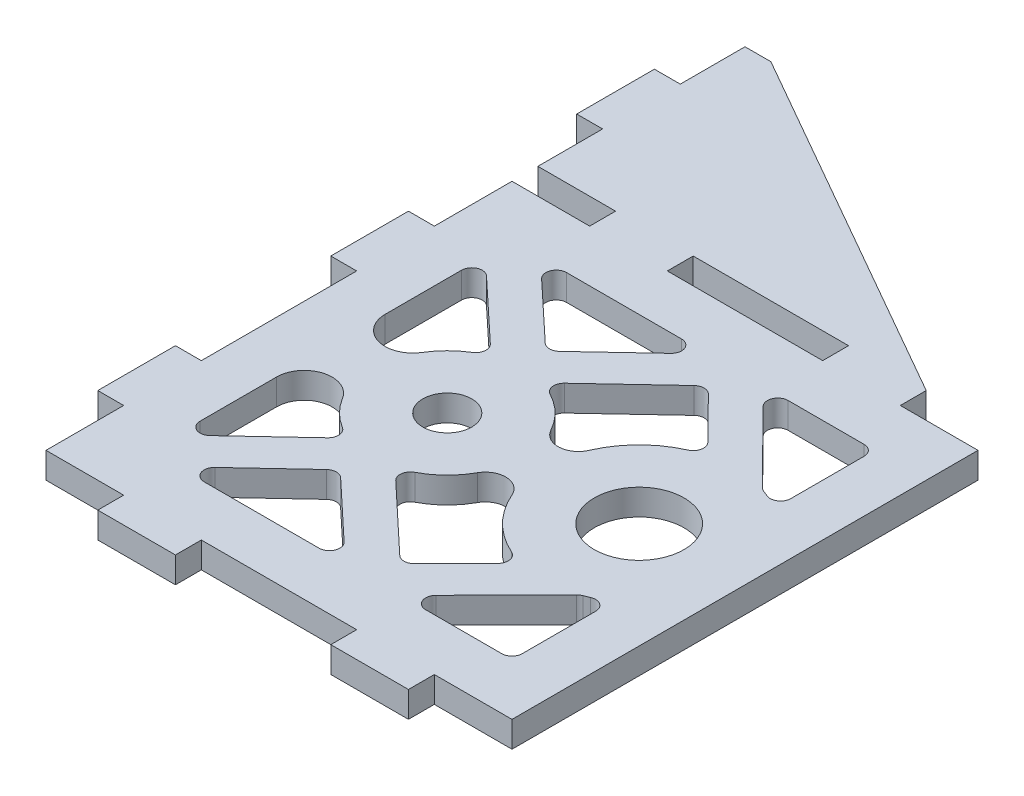
SolidWorks part; units mm, degrees
ref_plane "Front Plane" through (0, 0, 0) normal (0, 0, 1) x (1, 0, 0)
ref_plane "Top Plane" through (0, 0, 0) normal (0, 1, 0) x (1, 0, 0)
ref_plane "Right Plane" through (0, 0, 0) normal (1, 0, 0) x (0, 0, -1)
sketch "Sketch1" plane through (0, 0, 0) normal (0, 1, 0) x (1, 0, 0)
  line L0 (0, 57.15) -> (184.6638, 57.15) construction
  line L1 (0, 0) -> (19.05, 0)
  line L2 (0, 0) -> (0, 19.05)
  line L3 (0, 114.3) -> (19.05, 114.3)
  line L4 (114.3, 0) -> (114.3, 114.3)
  line L5 (38.1, 0) -> (76.2, 0)
  line L7 (95.25, 0) -> (95.25, -6.35)
  line L8 (95.25, -6.35) -> (76.2, -6.35)
  line L9 (76.2, 0) -> (76.2, -6.35)
  line L11 (19.05, 0) -> (19.05, -6.35)
  line L12 (19.05, -6.35) -> (38.1, -6.35)
  line L13 (38.1, 0) -> (38.1, -6.35)
  line L14 (95.25, 0) -> (114.3, 0)
  line L15 (38.1, 114.3) -> (38.1, 120.65)
  line L16 (19.05, 120.65) -> (38.1, 120.65)
  line L17 (19.05, 114.3) -> (19.05, 120.65)
  line L18 (76.2, 114.3) -> (76.2, 120.65)
  line L19 (95.25, 120.65) -> (76.2, 120.65)
  line L20 (95.25, 114.3) -> (95.25, 120.65)
  line L21 (38.1, 114.3) -> (76.2, 114.3)
  line L23 (95.25, 114.3) -> (114.3, 114.3)
  line L24 (-6.35, 19.05) -> (-6.35, 38.1)
  line L25 (0, 95.25) -> (-6.35, 95.25)
  line L27 (0, 76.2) -> (-6.35, 76.2)
  line L28 (-6.35, 95.25) -> (-6.35, 76.2)
  line L29 (0, 38.1) -> (-6.35, 38.1)
  line L31 (0, 19.05) -> (-6.35, 19.05)
  line L32 (0, 95.25) -> (0, 114.3)
  line L33 (0, 38.1) -> (0, 76.2)
  dimension "D1" = 114.3
  dimension "D2" = 114.3
  dimension "D3" = 19.05
  dimension "D4" = 19.05
  dimension "D5" = 19.05
  dimension "D6" = 19.05
  dimension "D7" = 6.35
  dimension "D8" = 6.35
  dimension "D9" = 19.05
  dimension "D10" = 19.05
extrude "Boss-Extrude1" add sketch "Sketch1" against normal blind 6.35
sketch "Sketch5" plane through (0, 0, 0) normal (0, 1, 0) x (1, 0, 0)
  line L0 (114.3, 57.15) -> (5.9998, 57.15) construction
  line L1 (114.3, 0) -> (114.3, 114.3) construction
  line L2 (3.175, 78.7113) -> (3.175, 29.9896) construction
  line L3 (0, 76.2) -> (0, 38.1) construction
  circle A0 centre (88.3412, 57.15) radius 10.16 construction
  circle A1 centre (41.275, 57.15) radius 38.1 construction
  dimension "D1" = 20.32
  dimension "D2" = 76.2
  dimension "D4" = 3.175
  dimension "D3" = 47.0662
sketch "Sketch2" plane through (0, 0, 0) normal (0, 1, 0) x (1, 0, 0)
  circle A2 centre (88.3412, 57.15) radius 11
  circle A3 centre (88.3412, 57.15) radius 10.16 construction
  circle A4 centre (88.3412, 57.15) radius 10.16 construction
  circle A5 centre (41.275, 57.15) radius 38.1 construction
  circle A6 centre (41.275, 57.15) radius 38.1 construction
  circle A7 centre (41.275, 57.15) radius 6
  dimension "D1" = 12
  dimension "D2" = 22
extrude "Cut-Extrude1" cut sketch "Sketch2" against normal through all
sketch "Sketch6" plane through (0, 0, 0) normal (0, 1, 0) x (1, 0, 0)
  line L28 (12.7, 101.6) -> (40.2169, 75.82) construction
  line L29 (15.9561, 105.0755) -> (43.4731, 79.2955)
  line L30 (9.4439, 98.1245) -> (36.9608, 72.3445)
  line L31 (40.2169, 75.82) -> (67.6542, 101.6) construction
  line L32 (36.9558, 79.2908) -> (64.393, 105.0708)
  line L33 (43.4781, 72.3492) -> (70.9153, 98.1292)
  line L34 (67.6542, 101.6) -> (96.5648, 72.3492) construction
  line L35 (71.0414, 104.9478) -> (99.952, 75.6971)
  line L36 (64.2669, 98.2522) -> (93.1776, 69.0014)
  line L37 (12.7, 57.15) -> (101.6, 57.15) construction
  line L38 (12.7, 12.7) -> (40.2169, 38.48) construction
  line L39 (15.9561, 9.2245) -> (43.4731, 35.0045)
  line L40 (9.4439, 16.1755) -> (36.9608, 41.9555)
  line L41 (40.2169, 38.48) -> (67.6542, 12.7) construction
  line L42 (36.9558, 35.0092) -> (64.393, 9.2292)
  line L43 (43.4781, 41.9508) -> (70.9153, 16.1708)
  line L44 (67.6542, 12.7) -> (96.5648, 41.9508) construction
  line L45 (71.0414, 9.3522) -> (99.952, 38.6029)
  line L46 (64.2669, 16.0478) -> (93.1776, 45.2986)
  line L56 (12.7, 12.7) -> (101.6, 12.7)
  line L57 (101.6, 12.7) -> (101.6, 101.6)
  line L58 (101.6, 101.6) -> (12.7, 101.6)
  line L59 (12.7, 101.6) -> (12.7, 12.7)
  line L60 (12.7, 12.7) -> (101.6, 12.7)
  line L61 (101.6, 12.7) -> (101.6, 101.6)
  line L62 (101.6, 101.6) -> (12.7, 101.6)
  line L63 (12.7, 101.6) -> (12.7, 12.7)
  circle A8 centre (41.275, 57.15) radius 18.7
  circle A9 centre (41.275, 57.15) radius 18.7
  arc A10 (57.6599, 66.1625) -> (66.5986, 66.5812) centre (62.0265, 68.5644) ccw
  circle A11 centre (88.3412, 57.15) radius 23.7
  circle A12 centre (88.3412, 57.15) radius 23.7
  arc A13 (12.7, 70.4558) -> (25.3203, 66.9038) centre (19.51, 70.4558) ccw
  arc A14 (15.9561, 105.0755) -> (9.4439, 98.1245) centre (12.7, 101.6) ccw
  arc A15 (36.9608, 72.3445) -> (43.4731, 79.2955) centre (40.2169, 75.82) ccw
  arc A16 (36.9558, 79.2908) -> (43.4781, 72.3492) centre (40.2169, 75.82) ccw
  arc A17 (70.9153, 98.1292) -> (64.393, 105.0708) centre (67.6542, 101.6) ccw
  arc A18 (71.0414, 104.9478) -> (64.2669, 98.2522) centre (67.6542, 101.6) ccw
  arc A19 (93.1776, 69.0014) -> (99.952, 75.6971) centre (96.5648, 72.3492) ccw
  arc A20 (15.9561, 9.2245) -> (9.4439, 16.1755) centre (12.7, 12.7) cw
  arc A21 (36.9608, 41.9555) -> (43.4731, 35.0045) centre (40.2169, 38.48) cw
  arc A22 (36.9558, 35.0092) -> (43.4781, 41.9508) centre (40.2169, 38.48) cw
  arc A23 (70.9153, 16.1708) -> (64.393, 9.2292) centre (67.6542, 12.7) cw
  arc A24 (71.0414, 9.3522) -> (64.2669, 16.0478) centre (67.6542, 12.7) cw
  arc A25 (93.1776, 45.2986) -> (99.952, 38.6029) centre (96.5648, 41.9508) cw
  arc A26 (57.6599, 48.1375) -> (66.5986, 47.7188) centre (62.0265, 45.7356) cw
  arc A27 (12.7, 43.8442) -> (25.3203, 47.3962) centre (19.51, 43.8442) cw
  point P11 (26.4585, 88.71)
  point P19 (53.9356, 88.71)
  point P29 (82.1095, 86.9746)
  point P37 (26.4585, 25.59)
  point P46 (53.9356, 25.59)
  point P53 (82.1095, 27.3254)
  dimension "D4" = 4.7625
  dimension "D1" = 12.7
  dimension "D2" = 12.7
  dimension "D3" = 12.7
extrude "Cut-Extrude3" cut sketch "Sketch6" against normal through all contours L63 A13 A9 L30 | L32 L62 L29 | A12 L36 L33 A9 A10 | A12 L61 L62 L35 | A26 A9 L43 L46 A12 | A27 L63 L40 A9 | L39 L60 L42 | A12 L45 L60 L61 region at (40.1924, 0, -95.1835) region at (20.3109, 0, -76.8897) region at (20.3109, 0, -37.4103) region at (64.292, 0, -78.8297) region at (92.3545, 0, -92.7594) region at (40.1924, 0, -19.1165) region at (64.292, 0, -35.4703) region at (92.3545, 0, -21.5406)
fillet "Fillet2" radius 2.54 24 edges at (82.2529, -3.175, -34.2454) (67.5312, -3.175, -19.3505) (46.4321, -3.175, -39.1752) (46.4321, -3.175, -75.1248) (67.5312, -3.175, -94.9495) (82.2529, -3.175, -80.0546) (12.7, -3.175, -19.2261) (34.5532, -3.175, -74.6001) (12.7, -3.175, -95.0739) (101.6, -3.175, -37.5058) (101.6, -3.175, -12.7) (74.3503, -3.175, -12.7) (96.1761, -3.175, -34.7825) (40.2122, -3.175, -31.9495) (60.6991, -3.175, -12.7) (19.6658, -3.175, -12.7) (19.6658, -3.175, -101.6) (60.6991, -3.175, -101.6) (40.2122, -3.175, -82.3505) (96.1761, -3.175, -79.5175) (74.3503, -3.175, -101.6) (101.6, -3.175, -101.6) (101.6, -3.175, -76.7942) (34.5532, -3.175, -39.6999)
sketch "Sketch3" [suppressed] plane through (0, 0, 0) normal (0, 1, 0) x (1, 0, 0)
  line L0 (90.7, 57.15) -> (-12.2602, 122.2732) construction
  line L1 (87.3056, 51.7834) -> (-15.6546, 116.9066)
  line L2 (94.0944, 62.5166) -> (-8.8658, 127.6398)
  line L3 (90.7, 57.15) -> (22.3264, 57.15) construction
  line L4 (90.7, 57.15) -> (-12.2602, -7.9732) construction
  line L5 (87.3056, 62.5166) -> (-15.6546, -2.6066)
  line L6 (94.0944, 51.7834) -> (-8.8658, -13.3398)
  line L35 (90.7, 57.15) -> (-12.2602, 57.15) construction
  line L36 (90.7, 50.8) -> (-12.2602, 50.8)
  line L37 (90.7, 63.5) -> (-12.2602, 63.5)
  line L63 (12.7, 12.7) -> (101.6, 12.7)
  line L64 (101.6, 12.7) -> (101.6, 101.6)
  line L65 (101.6, 101.6) -> (12.7, 101.6)
  line L66 (12.7, 101.6) -> (12.7, 12.7)
  line L67 (12.7, 12.7) -> (101.6, 12.7)
  line L68 (101.6, 12.7) -> (101.6, 101.6)
  line L69 (101.6, 101.6) -> (12.7, 101.6)
  line L70 (12.7, 101.6) -> (12.7, 12.7)
  arc A0 (87.3056, 51.7834) -> (94.0944, 62.5166) centre (90.7, 57.15) ccw
  arc A1 (-8.8658, 127.6398) -> (-15.6546, 116.9066) centre (-12.2602, 122.2732) ccw
  arc A3 (87.3056, 62.5166) -> (94.0944, 51.7834) centre (90.7, 57.15) cw
  circle A4 centre (90.7, 57.15) radius 29.95
  circle A5 centre (90.7, 57.15) radius 29.95
  arc A6 (-8.8658, -13.3398) -> (-15.6546, -2.6066) centre (-12.2602, -7.9732) cw
  arc A7 (90.7, 50.8) -> (90.7, 63.5) centre (90.7, 57.15) ccw
  arc A8 (-12.2602, 63.5) -> (-12.2602, 50.8) centre (-12.2602, 57.15) ccw
  point P2 (39.2199, 89.7116)
  point P8 (39.2199, 24.5884)
  point P19 (39.2199, 57.15)
  dimension "D2" = 6.35
  dimension "D1" = 12.7
  dimension "D3" = 12.7
extrude "Cut-Extrude2" [suppressed] cut sketch "Sketch3" against normal through all contours A5 L68 L69 L2 | A5 L1 L70 L37 | A5 L36 L70 L5 | A5 L6 L67 L68
fillet "Fillet1" [suppressed] radius 2.54
sketch "Sketch4" plane through (0, 0, 0) normal (0, 1, 0) x (1, 0, 0)
  line L0 (0, 171.45) -> (6.35, 171.45)
  line L1 (6.35, 171.45) -> (95.25, 120.65)
  line L2 (95.25, 120.65) -> (76.2, 120.65) construction
  line L3 (0, 120.65) -> (0, 136.525)
  line L4 (0, 114.3) -> (0, 95.25) construction
  line L9 (19.05, 114.3) -> (0, 114.3) construction
  line L10 (0, 155.575) -> (0, 171.45)
  line L11 (95.25, 114.3) -> (95.25, 120.65) construction
  line L12 (0, 120.65) -> (19.05, 120.65)
  line L13 (-6.35, 155.575) -> (-6.35, 136.525)
  line L14 (-6.35, 136.525) -> (0, 136.525)
  line L16 (0, 155.575) -> (-6.35, 155.575)
  line L17 (19.05, 120.65) -> (95.25, 120.65)
  dimension "D1" = 6.35
  dimension "D2" = 22.225
  dimension "D3" = 6.35
  dimension "D4" = 19.05
  dimension "D5" = 15.875
extrude "Boss-Extrude2" add sketch "Sketch4" against normal blind 6.35
